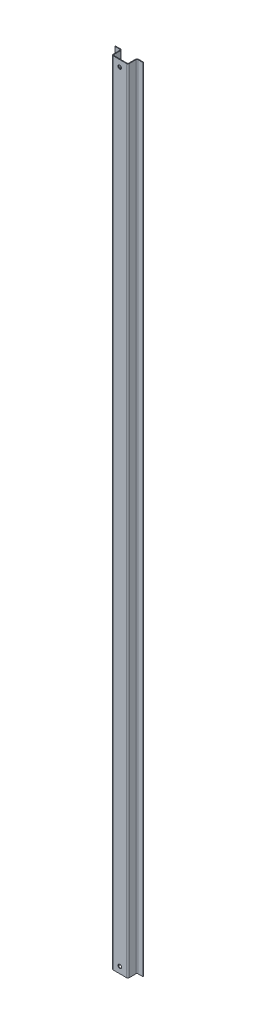
SolidWorks part; units mm, degrees
note: The reader was unsure of these and kept them because the rebuilt part matched: flange length of "Edge-Flange1", "Edge-Flange2".
material "Galvanized Steel"
ref_plane "Front" through (0, 0, 0) normal (0, 0, 1) x (1, 0, 0)
ref_plane "Top" through (0, 0, 0) normal (0, 1, 0) x (1, 0, 0)
ref_plane "Right" through (0, 0, 0) normal (1, 0, 0) x (0, 0, -1)
sketch "Sketch1" plane through (0, 0, 0) normal (0, 0, 1) x (1, 0, 0)
  line L1 (-25, -1221.5) -> (25, -1221.5)
  line L2 (-25, -1221.5) -> (-25, 1221.5)
  line L3 (-25, 1221.5) -> (25, 1221.5)
  line L4 (25, -1221.5) -> (25, 1221.5)
  line L5 (-25, -1221.5) -> (25, 1221.5) construction
  line L6 (-25, 1221.5) -> (25, -1221.5) construction
  point P0 (0, 0)
  dimension "D1" = 50
  dimension "D2" = 2443
base flange "Base-Flange1" sketch "Sketch1" thickness 2 reverse thickness direction no parameters "D1"=13
edge flange "Edge-Flange1" sketch "Sketch10" flange profiles "Sketch10", "Sketch11" flange angle 90 flange length 30 flange position material inside bend radius 2.5 thickness 2 relief rectangular parameters "D6"=10, "D8"=1
sketch "Sketch10" plane through (25, 0, -2) normal (-1, 0, 0) x (0, 1, 0)
  line L2 (-1221.5, 0) -> (-1221.5, 28)
  line L3 (-1221.5, 28) -> (1221.5, 28)
  line L4 (1221.5, 28) -> (1221.5, 0)
  line L5 (1221.5, 0) -> (-1221.5, 0) construction
  line L6 (1221.5, 0) -> (-1221.5, 0)
sketch "Sketch11" plane through (-25, 0, -2) normal (1, 0, 0) x (0, -1, 0)
  line L2 (-1221.5, 0) -> (-1221.5, 28)
  line L3 (-1221.5, 28) -> (1221.5, 28)
  line L4 (1221.5, 28) -> (1221.5, 0)
  line L5 (1221.5, 0) -> (-1221.5, 0) construction
  line L6 (1221.5, 0) -> (-1221.5, 0)
bend "EdgeBend1" bend radius 2.5 bend angle 90 parameters "D5"=1
bend "EdgeBend2" bend radius 2.5 bend angle 90 parameters "D5"=2
edge flange "Edge-Flange2" sketch "Sketch16" flange profiles "Sketch16", "Sketch17" flange angle 90 flange length 20 flange position material inside bend radius 2.5 thickness 2 relief rectangular parameters "D6"=10, "D8"=1
sketch "Sketch16" plane through (-25, 0, -30) normal (0, 0, -1) x (0, -1, 0)
  line L0 (1221.5, 0) -> (-1221.5, 0) construction
  line L1 (1221.5, 0) -> (-1221.5, 0)
  line L2 (-1221.5, 0) -> (-1221.5, 18)
  line L3 (-1221.5, 18) -> (1221.5, 18)
  line L4 (1221.5, 18) -> (1221.5, 0)
sketch "Sketch17" plane through (25, 0, -30) normal (0, 0, -1) x (0, 1, 0)
  line L0 (1221.5, 0) -> (-1221.5, 0) construction
  line L1 (1221.5, 0) -> (-1221.5, 0)
  line L2 (-1221.5, 0) -> (-1221.5, 18)
  line L3 (-1221.5, 18) -> (1221.5, 18)
  line L4 (1221.5, 18) -> (1221.5, 0)
bend "EdgeBend3" bend radius 2.5 bend angle 90 parameters "D5"=3
bend "EdgeBend4" bend radius 2.5 bend angle 90 parameters "D5"=4
sketch "Sketch18" plane through (0, 0, -2) normal (0, 0, -1) x (-1, 0, 0)
  line L0 (-20.5, 1221.5) -> (20.5, 1221.5) construction
  circle A0 centre (0, 1201.5) radius 5.5
  dimension "D1" = 11
  dimension "D2" = 20
extrude "Cut-Extrude1" cut sketch "Sketch18" against normal blind 10 normal cut yes
mirror "Mirror1" about plane through (0, 0, 0) normal (0, 1, 0) of "Cut-Extrude1"
sketch "Bend-Lines1" [suppressed] plane through (0, 0, 0) normal (0, 1, 0) x (1, 0, 0)
sketch "Bounding-Box1" [suppressed] plane through (0, 0, 0) normal (0, 1, 0) x (1, 0, 0)
sheet metal parameters "Sheet-Metal1" thickness 2 parameters "D1"=13
flat pattern "Flat-Pattern1" [suppressed]
sketch "Bend-Lines2" plane through (0, 0, 0) normal (0, 1, 0) x (1, 0, 0)
sketch3d "Bounding-Box2" [suppressed]
  line L0 (-20, 1500, 0) -> (-20, -1500, 0) construction
  line L1 (20, 1500, 0) -> (20, -1500, 0) construction
  line L2 (-20, 1500, 0) -> (20, 1500, 0) construction
  line L3 (-20, -1500, 0) -> (20, -1500, 0) construction
sheet metal parameters "Sheet-Metal2" thickness 2 parameters "D1"=13
flat pattern "Flat-Pattern1"
sketch "Bend-Lines2" plane through (0, 0, 0) normal (0, 0, 1) x (1, 0, 0)
  line L0 (-18.2489, 1500) -> (-18.2489, -1500) construction
  line L1 (18.2489, -1500) -> (18.2489, 1500) construction
  line L2 (-18.2489, 1500) -> (-18.2489, -1500) construction
  line L3 (18.2489, -1500) -> (18.2489, 1500) construction
sketch3d "Bounding-Box2" [suppressed]
  line L0 (46.4978, 1500, 0) -> (46.4978, -1500, 0) construction
  line L1 (-46.4978, 1500, 0) -> (-46.4978, -1500, 0) construction
  line L2 (46.4978, 1500, 0) -> (-46.4978, 1500, 0) construction
  line L3 (46.4978, -1500, 0) -> (-46.4978, -1500, 0) construction
bend of the flat pattern "Flatten-<EdgeBend1>1"
bend of the flat pattern "Flatten-<EdgeBend2>1"
sheet metal parameters "Sheet-Metal3" thickness 2 parameters "D1"=13
flat pattern "Flat-Pattern1"
sketch "Bend-Lines2" plane through (0, 0, 0) normal (0, 0, 1) x (1, 0, 0)
  line L0 (-23.2489, 1221.5) -> (-23.2489, -1221.5) construction
  line L1 (23.2489, -1221.5) -> (23.2489, 1221.5) construction
  line L2 (-23.2489, 1221.5) -> (-23.2489, -1221.5) construction
  line L3 (23.2489, -1221.5) -> (23.2489, 1221.5) construction
  line L4 (49.7467, -1221.5) -> (49.7467, 1221.5) construction
  line L5 (-49.7467, 1221.5) -> (-49.7467, -1221.5) construction
  line L6 (49.7467, -1221.5) -> (49.7467, 1221.5) construction
  line L7 (-49.7467, 1221.5) -> (-49.7467, -1221.5) construction
sketch3d "Bounding-Box2" [suppressed]
  line L0 (67.9956, 1221.5, 0) -> (67.9956, -1221.5, 0) construction
  line L1 (-67.9956, 1221.5, 0) -> (-67.9956, -1221.5, 0) construction
  line L2 (67.9956, 1221.5, 0) -> (-67.9956, 1221.5, 0) construction
  line L3 (67.9956, -1221.5, 0) -> (-67.9956, -1221.5, 0) construction
bend of the flat pattern "Flatten-<EdgeBend1>1"
bend of the flat pattern "Flatten-<EdgeBend2>1"
bend of the flat pattern "Flatten-<EdgeBend3>1"
bend of the flat pattern "Flatten-<EdgeBend4>1"
sheet metal parameters "Sheet-Metal4" thickness 2 parameters "D1"=13
flat pattern "Flat-Pattern1"
sketch "Bend-Lines2" plane through (0, 0, 0) normal (0, 0, 1) x (1, 0, 0)
  line L0 (-23.2489, 1221.5) -> (-23.2489, -1221.5) construction
  line L1 (23.2489, -1221.5) -> (23.2489, 1221.5) construction
  line L2 (-23.2489, 1221.5) -> (-23.2489, -1221.5) construction
  line L3 (23.2489, -1221.5) -> (23.2489, 1221.5) construction
  line L4 (49.7467, -1221.5) -> (49.7467, 1221.5) construction
  line L5 (-49.7467, 1221.5) -> (-49.7467, -1221.5) construction
  line L6 (49.7467, -1221.5) -> (49.7467, 1221.5) construction
  line L7 (-49.7467, 1221.5) -> (-49.7467, -1221.5) construction
sketch3d "Bounding-Box2" [suppressed]
  line L0 (67.9956, 1221.5, 0) -> (67.9956, -1221.5, 0) construction
  line L1 (-67.9956, 1221.5, 0) -> (-67.9956, -1221.5, 0) construction
  line L2 (67.9956, 1221.5, 0) -> (-67.9956, 1221.5, 0) construction
  line L3 (67.9956, -1221.5, 0) -> (-67.9956, -1221.5, 0) construction
bend of the flat pattern "Flatten-<EdgeBend1>1"
bend of the flat pattern "Flatten-<EdgeBend2>1"
bend of the flat pattern "Flatten-<EdgeBend3>1"
bend of the flat pattern "Flatten-<EdgeBend4>1"
sheet metal parameters "Sheet-Metal5" thickness 2 parameters "D1"=13
flat pattern "Flat-Pattern1"
sketch "Bend-Lines2" plane through (0, 0, 0) normal (0, 0, 1) x (1, 0, 0)
  line L0 (-23.2489, 1221.5) -> (-23.2489, -1221.5) construction
  line L1 (23.2489, -1221.5) -> (23.2489, 1221.5) construction
  line L2 (-23.2489, 1221.5) -> (-23.2489, -1221.5) construction
  line L3 (23.2489, -1221.5) -> (23.2489, 1221.5) construction
  line L4 (49.7467, -1221.5) -> (49.7467, 1221.5) construction
  line L5 (-49.7467, 1221.5) -> (-49.7467, -1221.5) construction
  line L6 (49.7467, -1221.5) -> (49.7467, 1221.5) construction
  line L7 (-49.7467, 1221.5) -> (-49.7467, -1221.5) construction
sketch3d "Bounding-Box2" [suppressed]
  line L0 (67.9956, 1221.5, 0) -> (67.9956, -1221.5, 0) construction
  line L1 (-67.9956, 1221.5, 0) -> (-67.9956, -1221.5, 0) construction
  line L2 (67.9956, 1221.5, 0) -> (-67.9956, 1221.5, 0) construction
  line L3 (67.9956, -1221.5, 0) -> (-67.9956, -1221.5, 0) construction
bend of the flat pattern "Flatten-<EdgeBend1>1"
bend of the flat pattern "Flatten-<EdgeBend2>1"
bend of the flat pattern "Flatten-<EdgeBend3>1"
bend of the flat pattern "Flatten-<EdgeBend4>1"
